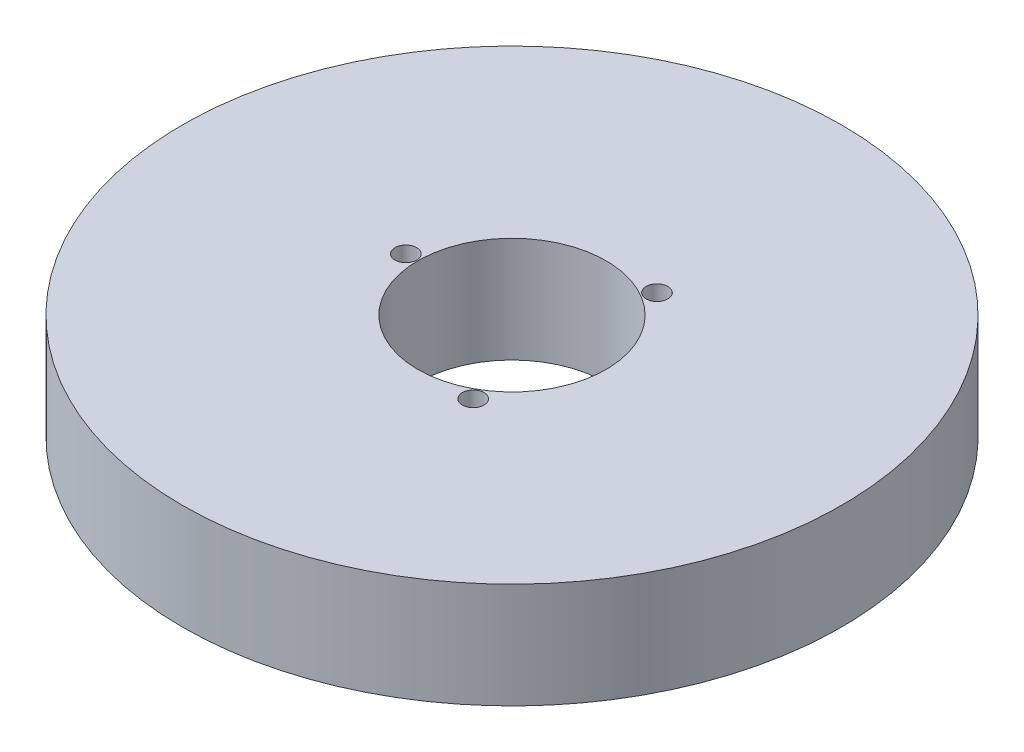
SolidWorks part; units mm, degrees
ref_plane "Front Plane" through (0, 0, 0) normal (0, 0, 1) x (1, 0, 0)
ref_plane "Top Plane" through (0, 0, 0) normal (0, 1, 0) x (1, 0, 0)
ref_plane "Right Plane" through (0, 0, 0) normal (1, 0, 0) x (0, 0, -1)
sketch "Sketch1" plane through (0, 0, 0) normal (0, 1, 0) x (1, 0, 0)
  circle A0 centre (0, 0) radius 87.5
  dimension "FLANGE_OD" = 175
extrude "Boss-Extrude1" add sketch "Sketch1" along normal blind 28
sketch "Sketch2" plane through (0, 0, 0) normal (0, 1, 0) x (1, 0, 0)
  circle A0 centre (0, 0) radius 25
  dimension "BORE_D" = 50
extrude "Cut-Extrude1" cut sketch "Sketch2" along normal through all
sketch "Sketch3" plane through (0, 28, 0) normal (0, 1, 0) x (1, 0, 0)
  circle A0 centre (0, 0) radius 28.1784 construction
  circle A1 centre (-28.1784, 0) radius 2.8795
  dimension "BOLT_D" = 5.7591
  dimension "BOLT_PCD" = 56.3569
extrude "Cut-Extrude2" cut sketch "Sketch3" against normal blind 25.3522
pattern_circular "CirPattern1" count 3 over 360 about axis through (0, 0, 0) along (0, 1, 0) of "Cut-Extrude2"
